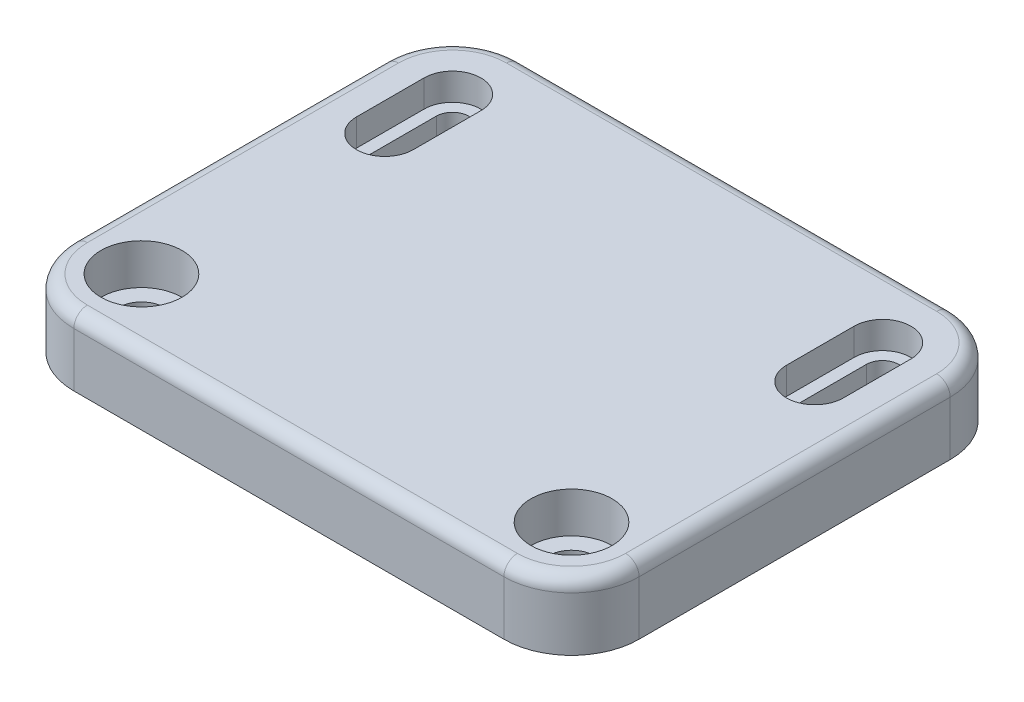
SolidWorks part; units mm, degrees
ref_plane "Front Plane" through (0, 0, 0) normal (0, 0, 1) x (1, 0, 0)
ref_plane "Top Plane" through (0, 0, 0) normal (0, 1, 0) x (1, 0, 0)
ref_plane "Right Plane" through (0, 0, 0) normal (1, 0, 0) x (0, 0, -1)
sketch "Sketch1" plane through (0, 0, 0) normal (0, 1, 0) x (1, 0, 0)
  line L0 (5, 23) -> (5, 28) construction
  line L1 (0, 0) -> (41.8, 0)
  line L2 (0, 0) -> (0, 33)
  line L3 (0, 33) -> (41.8, 33)
  line L4 (41.8, 0) -> (41.8, 33)
  line L5 (5, 23) -> (36.8, 23) construction
  line L6 (5, 23) -> (5, 5) construction
  line L7 (5, 5) -> (36.8, 5) construction
  line L8 (36.8, 23) -> (36.8, 5) construction
  line L9 (3.8, 23) -> (3.8, 28)
  line L10 (6.2, 23) -> (6.2, 28)
  line L11 (36.8, 23) -> (36.8, 28) construction
  line L12 (35.6, 23) -> (35.6, 28)
  line L13 (38, 23) -> (38, 28)
  line L14 (0, 0) -> (5, 5) construction
  line L15 (36.8, 5) -> (41.8, 0) construction
  circle A0 centre (5, 5) radius 1.7
  circle A1 centre (36.8, 5) radius 1.7
  arc A2 (3.8, 23) -> (6.2, 23) centre (5, 23) ccw
  arc A3 (6.2, 28) -> (3.8, 28) centre (5, 28) ccw
  arc A4 (35.6, 23) -> (38, 23) centre (36.8, 23) ccw
  arc A5 (38, 28) -> (35.6, 28) centre (36.8, 28) ccw
  point P11 (5, 25.5)
  point P17 (36.8, 25.5)
  dimension "D1" = 1.2
  dimension "D2" = 3.4
  dimension "D3" = 31.8
  dimension "D4" = 18
  dimension "D5" = 5
  dimension "D6" = 5
  dimension "D7" = 5
  dimension "D8" = 5
extrude "Boss-Extrude1" add sketch "Sketch1" along normal blind 5
fillet "Fillet1" radius 5 4 edges at (0, 2.5, -33) (41.8, 2.5, -33) (41.8, 2.5, 0) (0, 2.5, 0)
fillet "Fillet2" radius 1 8 edges at (1.4645, 5, -1.4645) (0, 5, -16.5) (1.4645, 5, -31.5355) (20.9, 5, -33) (40.3355, 5, -31.5355) (41.8, 5, -16.5) (40.3355, 5, -1.4645) (20.9, 5, 0)
sketch "Sketch2" plane through (0, 5, 0) normal (0, 1, 0) x (1, 0, 0)
  line L0 (5, 28) -> (5, 23) construction
  line L1 (7.1, 28) -> (7.1, 23)
  line L2 (2.9, 28) -> (2.9, 23)
  line L3 (36.8, 28) -> (36.8, 23) construction
  line L4 (38.9, 28) -> (38.9, 23)
  line L5 (34.7, 28) -> (34.7, 23)
  circle A0 centre (5, 5) radius 3
  circle A1 centre (36.8, 5) radius 3
  arc A2 (7.1, 28) -> (2.9, 28) centre (5, 28) ccw
  arc A3 (2.9, 23) -> (7.1, 23) centre (5, 23) ccw
  arc A4 (38.9, 28) -> (34.7, 28) centre (36.8, 28) ccw
  arc A5 (34.7, 23) -> (38.9, 23) centre (36.8, 23) ccw
  point P10 (5, 25.5)
  point P15 (36.8, 25.5)
  arc M18 (6.2, 23) -> (3.8, 23) centre (5, 23) cw
  line M19 (3.8, 23) -> (3.8, 28)
  arc M20 (3.8, 28) -> (6.2, 28) centre (5, 28) cw
  line M21 (6.2, 28) -> (6.2, 23)
  circle M22 centre (5, 5) radius 1.7
  circle M23 centre (36.8, 5) radius 1.7
  arc M24 (38, 23) -> (35.6, 23) centre (36.8, 23) cw
  line M25 (35.6, 23) -> (35.6, 28)
  arc M26 (35.6, 28) -> (38, 28) centre (36.8, 28) cw
  line M27 (38, 28) -> (38, 23)
  dimension "D1" = 6
  dimension "D2" = 2.1
extrude "Cut-Extrude1" cut sketch "Sketch2" against normal blind 3 contours A0 M22 | A1 M23 region at (2.0849, 5, -5) region at (33.8849, 5, -5)
extrude "Cut-Extrude2" cut sketch "Sketch2<3>" against normal blind 2 contours L2 A3 L1 A2 M21 M18 M19 M20 | L5 A5 L4 A4 M27 M24 M25 M26 region at (6.9989, 5, -25.5) region at (38.7989, 5, -25.5)
sketch "Sketch2<3>" plane through (0, 5, 0) normal (0, 1, 0) x (1, 0, 0) same geometry as "Sketch2"
